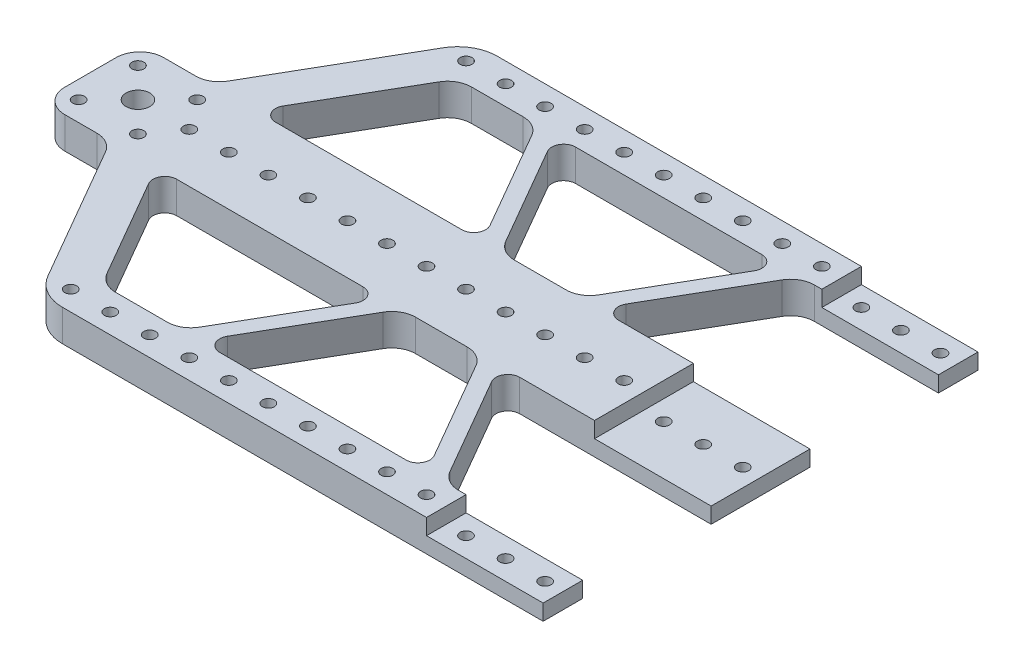
SolidWorks part; units mm, degrees
ref_plane "Front Plane" through (0, 0, 0) normal (0, 0, 1) x (1, 0, 0)
ref_plane "Top Plane" through (0, 0, 0) normal (0, 1, 0) x (1, 0, 0)
ref_plane "Right Plane" through (0, 0, 0) normal (1, 0, 0) x (0, 0, -1)
sketch "Sketch1" plane through (0, 0, 0) normal (0, 1, 0) x (1, 0, 0)
  line L0 (-80.25, 7.5) -> (-65.25, -7.5) construction
  line L1 (-84.75, -12.5) -> (84.75, -12.5)
  line L2 (-84.75, -12.5) -> (-84.75, 12.5)
  line L3 (-84.75, 12.5) -> (84.75, 12.5)
  line L4 (84.75, -12.5) -> (84.75, 12.5)
  line L5 (-84.75, -12.5) -> (84.75, 12.5) construction
  line L6 (-84.75, 12.5) -> (84.75, -12.5) construction
  line L7 (-65.25, 7.5) -> (-80.25, -7.5) construction
  line L8 (-80.25, 7.5) -> (-65.25, 7.5) construction
  line L9 (-67.1741, 12.5) -> (-42.6368, 55)
  line L10 (-42.6368, 55) -> (84.75, 55)
  line L11 (84.75, 55) -> (84.75, 45)
  line L12 (84.75, 45) -> (-36.8632, 45)
  line L13 (-36.8632, 45) -> (-55.6271, 12.5)
  line L14 (-42.6368, 55) -> (-36.8632, 45) construction
  line L15 (0, 0) -> (84.75, 0) construction
  line L16 (-39.75, 50) -> (84.75, 50) construction
  line L17 (-39.75, -50) -> (84.75, -50) construction
  line L18 (-42.6368, -55) -> (-36.8632, -45) construction
  line L19 (-36.8632, -45) -> (-55.6271, -12.5)
  line L20 (84.75, -45) -> (-36.8632, -45)
  line L21 (84.75, -55) -> (84.75, -45)
  line L22 (-67.1741, 12.5) -> (-55.6271, 12.5) construction
  line L23 (-42.6368, -55) -> (84.75, -55)
  line L24 (-67.1741, -12.5) -> (-42.6368, -55)
  line L25 (-16.8632, 45) -> (1.9006, 12.5)
  line L26 (1.9006, 12.5) -> (6.5194, 12.5)
  line L27 (6.5194, 12.5) -> (-12.2444, 45)
  line L28 (45.2833, 45) -> (26.5194, 12.5)
  line L29 (49.9021, 45) -> (31.1382, 12.5)
  line L30 (49.9021, -45) -> (31.1382, -12.5)
  line L31 (45.2833, -45) -> (26.5194, -12.5)
  line L32 (6.5194, -12.5) -> (-12.2444, -45)
  line L33 (-16.8632, -45) -> (1.9006, -12.5)
  line L34 (55.25, 55) -> (55.25, 45) construction
  line L35 (55.25, 55) -> (55.25, 45)
  line L36 (55.25, 12.5) -> (55.25, -12.5)
  line L37 (55.25, -45) -> (55.25, -55)
  circle A0 centre (-80.25, 7.5) radius 1.5
  circle A1 centre (-65.25, 7.5) radius 1.5
  circle A2 centre (-65.25, -7.5) radius 1.5
  circle A3 centre (-80.25, -7.5) radius 1.5
  circle A4 centre (-39.75, 50) radius 1.5
  circle A6 centre (-29.75, 50) radius 1.5
  circle A7 centre (-19.75, 50) radius 1.5
  circle A8 centre (-9.75, 50) radius 1.5
  circle A9 centre (0.25, 50) radius 1.5
  circle A10 centre (10.25, 50) radius 1.5
  circle A11 centre (20.25, 50) radius 1.5
  circle A12 centre (30.25, 50) radius 1.5
  circle A13 centre (40.25, 50) radius 1.5
  circle A14 centre (50.25, 50) radius 1.5
  circle A15 centre (60.25, 50) radius 1.5
  circle A16 centre (70.25, 50) radius 1.5
  circle A17 centre (80.25, 50) radius 1.5
  circle A26 centre (80.25, -50) radius 1.5
  circle A27 centre (70.25, -50) radius 1.5
  circle A28 centre (60.25, -50) radius 1.5
  circle A29 centre (50.25, -50) radius 1.5
  circle A30 centre (40.25, -50) radius 1.5
  circle A31 centre (30.25, -50) radius 1.5
  circle A32 centre (20.25, -50) radius 1.5
  circle A33 centre (10.25, -50) radius 1.5
  circle A34 centre (0.25, -50) radius 1.5
  circle A35 centre (-9.75, -50) radius 1.5
  circle A36 centre (-19.75, -50) radius 1.5
  circle A37 centre (-29.75, -50) radius 1.5
  circle A38 centre (-39.75, -50) radius 1.5
  circle A39 centre (80.25, 0) radius 1.5
  circle A40 centre (70.25, 0) radius 1.5
  circle A41 centre (60.25, 0) radius 1.5
  circle A42 centre (50.25, 0) radius 1.5
  circle A43 centre (40.25, 0) radius 1.5
  circle A44 centre (30.25, 0) radius 1.5
  circle A45 centre (20.25, 0) radius 1.5
  circle A46 centre (10.25, 0) radius 1.5
  circle A47 centre (0.25, 0) radius 1.5
  circle A48 centre (-9.75, 0) radius 1.5
  circle A49 centre (-19.75, 0) radius 1.5
  circle A50 centre (-29.75, 0) radius 1.5
  circle A51 centre (-39.75, 0) radius 1.5
  circle A52 centre (-49.75, 0) radius 1.5
  circle A53 centre (-59.75, 0) radius 1.5
  circle A54 centre (-72.75, 0) radius 3
  point P0 (0, 0)
  point P14 (-72.75, 0)
  point P15 (-72.75, 0)
  dimension "D3" = 3
  dimension "D10" = 3
  dimension "D21" = 6
  dimension "D1" = 169.5
  dimension "D2" = 25
  dimension "D4" = 12
  dimension "D5" = 10
  dimension "D6" = 10
  dimension "D7" = 60
  dimension "D8" = 120
  dimension "D9" = 15
  dimension "D13" = 4
  dimension "D14" = 4
  dimension "D15" = 20
  dimension "D16" = 20
  dimension "D17" = 60
  dimension "D18" = 60
  dimension "D19" = 110
  dimension "D20" = 45
  dimension "D22" = 10
  dimension "D23" = 10
  dimension "D24" = 15
  dimension "D12" = 4.5
  dimension "D11" = 13
extrude "Boss-Extrude1" add sketch "Sketch1" against normal blind 4 contours L35 L10 L9 L3 L13 L12 A14 A13 A12 A11 A10 A9 A8 A7 A6 A4 | L10 L35 L12 L11 A17 A16 A15 | L3 L36 L1 L4 A41 A40 A39 | L36 L3 L2 L1 A53 A52 A51 A50 A49 A48 A47 A46 A45 A44 A43 A42 A3 A2 A1 A0 | L29 L12 L28 L3 | L3 L27 L12 L25 | L33 L20 L32 L1 | L31 L20 L30 L1 | L37 L20 L19 L1 L24 L23 A33 A31 A29 A30 A32 A38 | L20 L37 L23 L21 A27 A26 A28 region at (-14.026, 0, 0) region at (-61.4006, 0, 13.7959) region at (-53.7832, 0, -33.102) region at (-5.1719, 0, 28.75) region at (55.5615, 0, 50) region at (-5.1719, 0, -28.75) region at (70, 0, -54.6885) region at (38.2108, 0, 28.75) region at (38.2108, 0, -28.75) region at (55.6367, 0, 0)
extrude "Boss-Extrude2" add sketch "Sketch1<4>" along normal blind 4 contours L35 L10 L9 L3 L13 L12 A14 A13 A12 A11 A10 A9 A8 A7 A6 A4 | L3 L27 L12 L25 | L29 L12 L28 L3 | L36 L3 L2 L1 A53 A52 A51 A50 A49 A48 A47 A46 A45 A44 A43 A42 A3 A2 A1 A0 | L31 L20 L30 L1 | L33 L20 L32 L1 | L37 L20 L19 L1 L24 L23 A33 A31 A29 A30 A32 A38 region at (-14.026, 0, 0) region at (-61.4006, 0, 13.7959) region at (-53.7832, 0, -33.102) region at (-5.1719, 0, 28.75) region at (-5.1719, 0, -28.75) region at (38.2108, 0, 28.75) region at (38.2108, 0, -28.75)
sketch "Sketch1<4>" plane through (0, 0, 0) normal (0, 1, 0) x (1, 0, 0) same geometry as "Sketch1"
fillet "Fillet1" radius 6 2 edges at (-84.75, 0, -12.5) (-84.75, 0, 12.5)
fillet "Fillet2" radius 6 12 edges at (26.5194, 0, 12.5) (6.5194, 0, 12.5) (26.5194, 0, -12.5) (6.5194, 0, -12.5) (-67.1741, 0, -12.5) (-67.1741, 0, 12.5) (-36.8632, 0, 45) (-16.8632, 0, 45) (49.9021, 0, 45) (49.9021, 0, -45) (-16.8632, 0, -45) (-36.8632, 0, -45)
fillet "Fillet3" radius 3 10 edges at (-55.6271, 0, -12.5) (-12.2444, 0, -45) (45.2833, 0, -45) (31.1382, 0, -12.5) (1.9006, 0, -12.5) (-55.6271, 0, 12.5) (-12.2444, 0, 45) (45.2833, 0, 45) (31.1382, 0, 12.5) (1.9006, 0, 12.5)
fillet "Fillet4" radius 10 2 edges at (-42.6368, 0, 55) (-42.6368, 0, -55)
